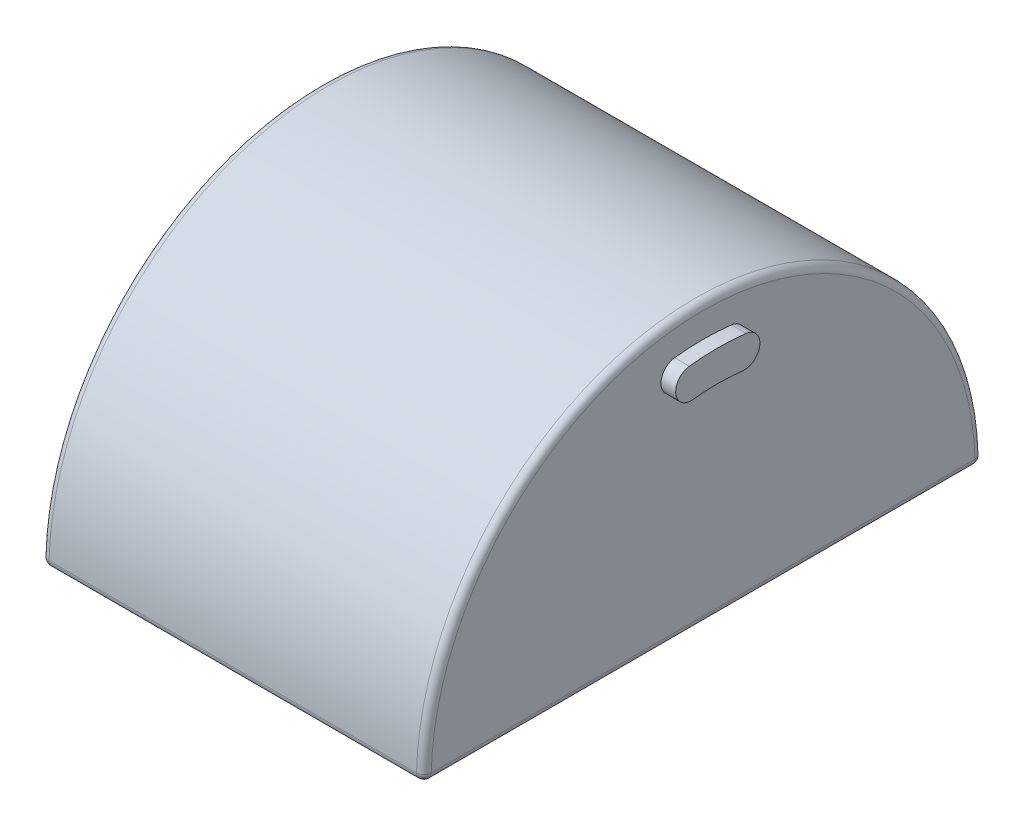
SolidWorks part; units mm, degrees
ref_plane "Front Plane" through (0, 0, 0) normal (0, 0, 1) x (1, 0, 0)
ref_plane "Top Plane" through (0, 0, 0) normal (0, 1, 0) x (1, 0, 0)
ref_plane "Right Plane" through (0, 0, 0) normal (1, 0, 0) x (0, 0, -1)
sketch "Sketch5" plane through (0, 0, 0) normal (0, 0, 1) x (1, 0, 0)
  line L0 (-13.97, 0) -> (13.97, 0)
  arc A0 (11.176, 0) -> (-11.176, 0) centre (0, 0) ccw
  arc A1 (12.7, 0) -> (-12.7, 0) centre (0, 0) ccw
  arc A2 (13.97, 0) -> (-13.97, 0) centre (0, 0) ccw
  arc A3 (12.446, 0) -> (-12.446, 0) centre (0, 0) ccw
  arc A4 (8.636, 0) -> (-8.636, 0) centre (0, 0) ccw
  dimension "D1" = 24.892
  dimension "D2" = 25.4
  dimension "D3" = 27.94
  dimension "D4" = 22.352
  dimension "D5" = 17.272
sketch "Sketch6" plane through (0, 0, 0) normal (1, 0, 0) x (0, 0, -1)
  line L0 (0, 20.0109) -> (1.905, 20.0109)
  line L1 (0, 20.0109) -> (-1.905, 20.0109)
  line L2 (0, 18.6774) -> (0, 0) construction
  line L3 (-24.1384, 0) -> (24.3191, 0)
  line L8 (24.3191, 0) -> (-24.3191, 0) construction
  arc A1 (24.1384, 0) -> (-24.1384, 0) centre (0, 0) ccw
  arc A5 (21.5984, 0) -> (-21.5984, 0) centre (0, 0) ccw
  arc A6 (18.4234, 0) -> (-18.4234, 0) centre (0, 0) ccw
  arc A7 (21.3444, 0) -> (-21.3444, 0) centre (0, 0) ccw construction
  arc A8 (18.6774, 0) -> (-18.6774, 0) centre (0, 0) ccw construction
  arc A11 (20.0109, 0) -> (-20.0109, 0) centre (0, 0) ccw construction
  arc A12 (-2.3038, 19.8778) -> (2.3038, 19.8778) centre (0, 0) cw construction
  arc A22 (2.4574, 21.2024) -> (-2.4574, 21.2024) centre (0, 0) ccw
  arc A23 (2.1503, 18.5532) -> (-2.1503, 18.5532) centre (0, 0) ccw
  arc A24 (2.1503, 18.5532) -> (2.4574, 21.2024) centre (2.3038, 19.8778) ccw
  arc A25 (-2.4574, 21.2024) -> (-2.1503, 18.5532) centre (-2.3038, 19.8778) ccw
  point P24 (0, 20.0109)
  point P25 (0, 20.0109)
  dimension "D1" = 43.1967
  dimension "D2" = 36.8467
  dimension "D8" = 40.0217
  dimension "D7" = 18.6774
  dimension "D9" = 24.1384
  dimension "D3" = 1.905
  dimension "D6" = 1.905
  dimension "D4" = 0.254
  dimension "D5" = 0.254
extrude "Main Body Extrude" add sketch "Sketch6" along normal mid plane 33.02 contours L8 A5 A7 | L8 A6 | L8 A8 A6 | L8 A7 A8 | L8 A1 A5 | A7 L3 A8 | A8 L3 A7 | A23 region at (0, 23.5986, 0) region at (0, 21.5501, 0) region at (0, 7.8191, 0)
extrude "Inner Hinge Cut" cut sketch "Sketch5<16>" against normal mid plane 30.48 contours L0 A2 A1 | L0 A3 A0 | A4 L0 A0 | L0 A4 | A3 L0 A1 region at (0, 13.6576, 0) region at (0, 12.6716, 0) region at (0, 12.1677, 0) region at (0, 10.9261, 0) region at (0, 3.6652, 0)
sketch "Sketch5<16>" plane through (0, 0, 0) normal (0, 0, 1) x (1, 0, 0) same geometry as "Sketch5"
extrude "Groove Cut" cut sketch "Sketch5" against normal mid plane 33.02 contours A4 L0 A0 region at (0, 10.9261, 0)
extrude "Slot 1 Extrude" add sketch "Sketch6<5>" along normal blind 1.27 from surface contours A22 A25 A23 A24 region at (0, 19.9388, 0) starting at face at (16.51, 19.8676, 0)
sketch "Sketch6<5>" plane through (0, 0, 0) normal (1, 0, 0) x (0, 0, -1) same geometry as "Sketch6"
extrude "Slot 2 Extrude" add sketch "Sketch6<6>" against normal blind 1.27 from surface contours L8 A7 A8 | A22 A25 A23 A24 region at (0, 19.9388, 0) starting at face at (-16.51, 19.8676, 0)
sketch "Sketch6<6>" plane through (0, 0, 0) normal (1, 0, 0) x (0, 0, -1) same geometry as "Sketch6"
fillet "Fillet1" radius 0.635 6 edges at (0, 0, -24.1384) (-16.51, 24.1384, 0) (-16.51, 0, 0) (16.51, 24.1384, 0) (16.51, 0, 0) (0, 0, 24.1384)
equation "\"D1@Sketch5\"=\"InnerBaseDiameter\""
equation "\"OuterBaseInnerGroove\"= \"OuterBaseOuterGroove\" - 0.25"
equation "\"D1@Sketch6\"=\"OuterBaseOuterGroove\""
equation "\"D2@Sketch6\"=\"OuterBaseInnerGroove\""
equation "\"D4@Sketch5\"=\"InnerBaseOuterGroove\""
equation "\"D5@Sketch5\"=\"InnerBaseInnerGroove\""
equation "\"D8@Sketch6\"=\"OuterBaseInnerGroove\" * 0.5 + \"OuterBaseOuterGroove\"*0.5"
equation "\"D7@Sketch6\"=\"OuterBaseInnerGroove\" * 0.5+0.01"
equation "\"InnerBaseDiameter\"=0.98"
equation "\"InnerBaseOuterGroove\"= \"InnerBaseDiameter\" - 0.1"
equation "\"InnerHingeInnerCurve\"= 1"
equation "\"InnerHingeOuterCurve\"= \"InnerHingeInnerCurve\" + 0.1"
equation "\"InnerBaseInnerGroove\"= \"InnerBaseOuterGroove\" - 0.2"
equation "\"InnerHingeWidth\"= 1.45"
equation "\"OuterBaseDiameter\"= ( ( \"InnerHingeOuterCurve\" / 2 ) ^ 2 + ( \"InnerHingeLength\" / 2 ) ^ 2 ) ^ 0.5 * 2"
equation "\"InnerHingeLength\"=1.55"
equation "\"OuterBaseOuterGroove\"= \"OuterBaseDiameter\" - 0.2"
equation "\"OuterHingeOuterDiameter\"= \"OuterHingeInnerDiameter\" + 0.2"
equation "\"OuterHingeInnerDiameter\"= \"OuterBaseDiameter\" + 0.05"
equation "\"OuterHingeLength\"= 1.3"
equation "\"TibiaConnectionLength\" = 1.25"
equation "\"D9@Sketch6\"=\"OuterBaseDiameter\"*0.5"
